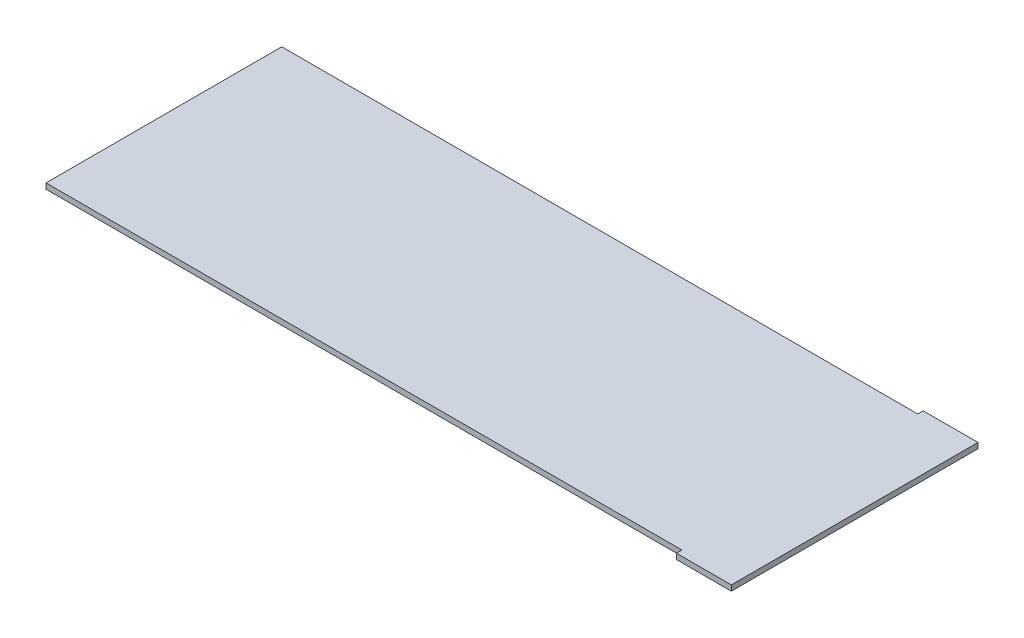
SolidWorks part; units mm, degrees
ref_plane "Front Plane" through (0, 0, 0) normal (0, 0, 1) x (1, 0, 0)
ref_plane "Top Plane" through (0, 0, 0) normal (0, 1, 0) x (1, 0, 0)
ref_plane "Right Plane" through (0, 0, 0) normal (1, 0, 0) x (0, 0, -1)
sketch "Sketch1" plane through (0, 0, 0) normal (0, 1, 0) x (1, 0, 0)
  line L1 (-200.025, 71.4375) -> (200.025, 71.4375)
  line L2 (-200.025, 71.4375) -> (-200.025, -71.4375)
  line L3 (-200.025, -71.4375) -> (200.025, -71.4375)
  line L4 (200.025, 71.4375) -> (200.025, -71.4375)
  line L5 (-200.025, 71.4375) -> (200.025, -71.4375) construction
  line L6 (-200.025, -71.4375) -> (200.025, 71.4375) construction
  line L7 (-200.025, -71.4375) -> (168.275, -71.4375)
  line L8 (-200.025, -71.4375) -> (-200.025, -68.2625)
  line L9 (-200.025, -68.2625) -> (168.275, -68.2625)
  line L10 (168.275, -71.4375) -> (168.275, -68.2625)
  line L11 (-200.025, 71.4375) -> (168.275, 71.4375)
  line L12 (-200.025, 71.4375) -> (-200.025, 68.2625)
  line L13 (-200.025, 68.2625) -> (168.275, 68.2625)
  line L14 (168.275, 71.4375) -> (168.275, 68.2625)
  point P0 (0, 0)
  dimension "D1" = 400.05
  dimension "D2" = 142.875
  dimension "D3" = 31.75
  dimension "D4" = 3.175
  dimension "D5" = 3.175
extrude "Boss-Extrude1" add sketch "Sketch1" along normal mid plane 3.175 contours L1 L14 L13 L2 L9 L10 L3 L4 region at (0.6773, 0, 0)
equation "\"D2@Sketch1\"   = 5.625in-(2*0.125in)"
equation "\"D1@Sketch1\"=16.00in-0.25in"
equation "\"D3@Sketch1\"=1.50in-0.25in"
